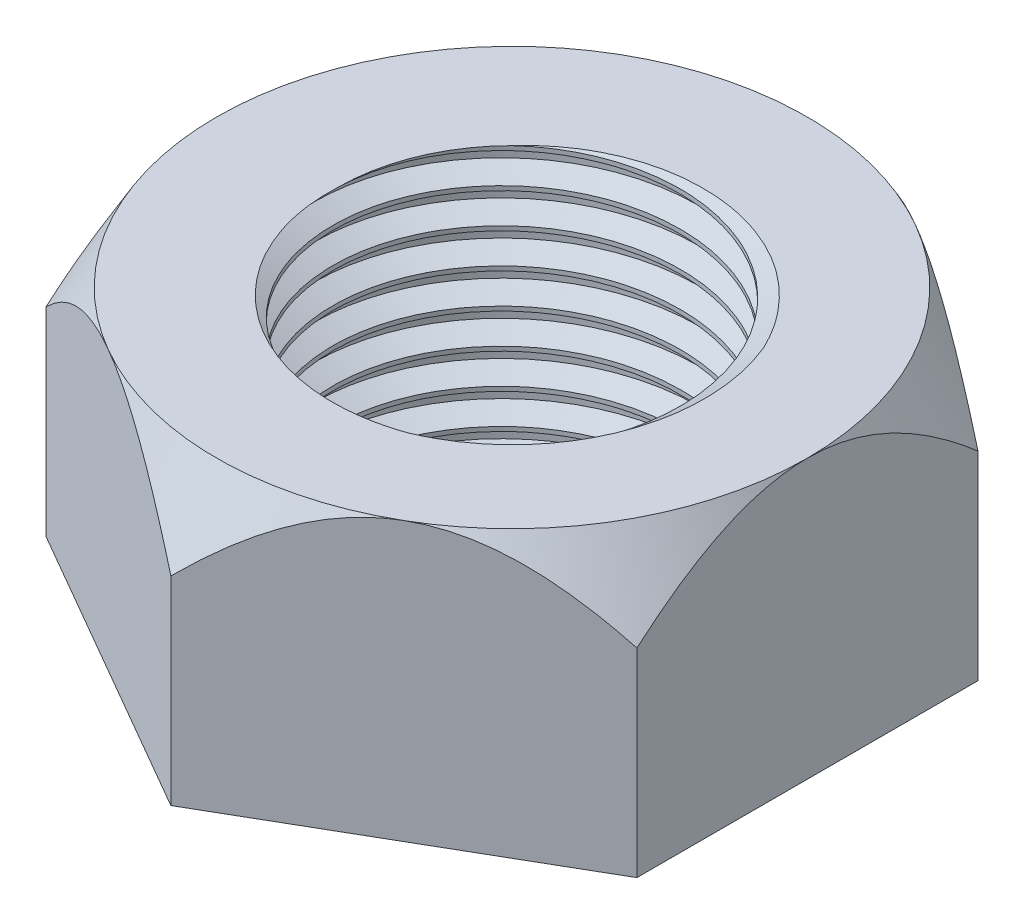
SolidWorks part; units mm, degrees
ref_plane "Front Plane" through (0, 0, 0) normal (0, 0, 1) x (1, 0, 0)
ref_plane "Top Plane" through (0, 0, 0) normal (0, 1, 0) x (1, 0, 0)
ref_plane "Right Plane" through (0, 0, 0) normal (1, 0, 0) x (0, 0, -1)
sketch "Sketch1" plane through (0, 0, 0) normal (0, 1, 0) x (1, 0, 0)
  line L1 (0, 9.815) -> (-8.5, 4.9075)
  line L2 (-8.5, 4.9075) -> (-8.5, -4.9075)
  line L3 (-8.5, -4.9075) -> (0, -9.815)
  line L4 (0, -9.815) -> (8.5, -4.9075)
  line L5 (8.5, -4.9075) -> (8.5, 4.9075)
  line L6 (8.5, 4.9075) -> (0, 9.815)
  circle A0 centre (0, 0) radius 5
  circle A1 centre (0, 0) radius 8.5 construction
  point P3 (0, 0)
  dimension "D2" = 10
  dimension "D1" = 17
extrude "Boss-Extrude1" add sketch "Sketch1" along normal blind 8
sketch "Sketch4" plane through (0, 8, 0) normal (0, 1, 0) x (1, 0, 0)
  line L0 (0, 9.815) -> (-8.5, 4.9075) construction
  circle A0 centre (0, 0) radius 8.5
extrude "Cut-Extrude1" cut sketch "Sketch4" against normal blind 12 draft 30 flip side to cut
thread "Thread1" pitch 1 method cut trim with start face yes trim with end face yes profile "Thread Profile1" start angle 0, offset 5, length 20, pitch 1, diameter 10
ref_plane "Plane1" through (-5, 13, 0) normal (0, 0, -1) x (1, 0, 0)
sketch "Thread Profile1" plane through (-5, 13, 0) normal (0, 0, -1) x (1, 0, 0)
  line L0 (0, 0) -> (0, 1) construction
  line L11 (0, 0) -> (0, 0.875)
  line L12 (0, 0.875) -> (-0.5413, 0.5625)
  line L13 (-0.5413, 0.5625) -> (-0.5413, 0.3125)
  line L15 (-0.5413, 0.3125) -> (0, 0)
  line L17 (-0.5413, 0.4375) -> (0, 0.4375) construction
  point P2 (0, 0)
  dimension "Pitch" = 1
  dimension "Profile_Angle" = 60
  dimension "Profile_Land" = 0.25
  dimension "Profile_Height" = 0.5413
